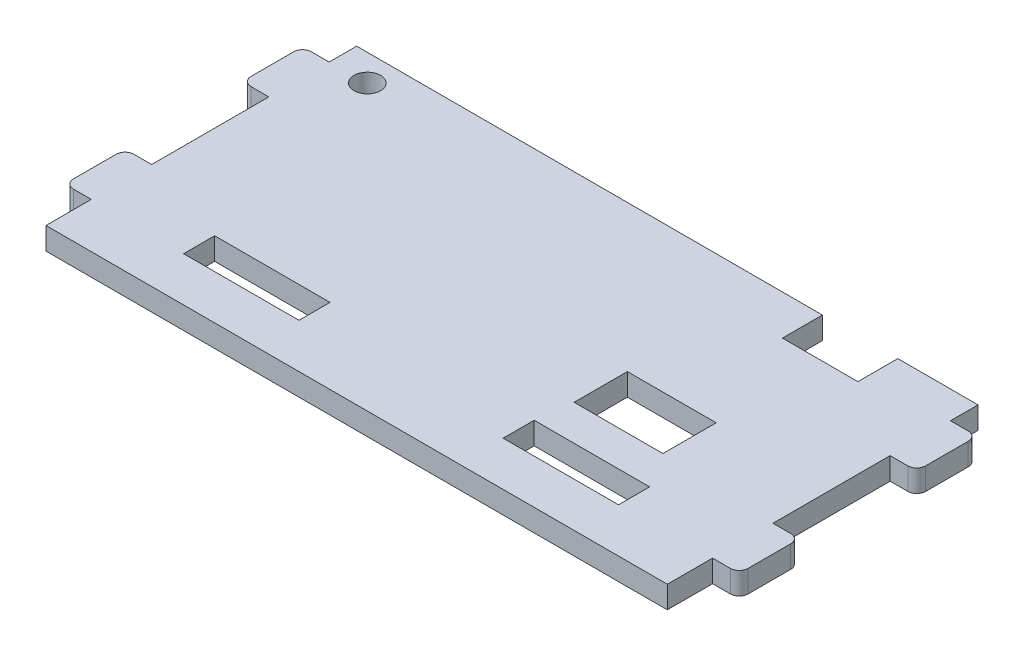
SolidWorks part; units mm, degrees
ref_plane "前视" through (0, 0, 0) normal (0, 0, 1) x (1, 0, 0)
ref_plane "上视" through (0, 0, 0) normal (0, 1, 0) x (1, 0, 0)
ref_plane "右视" through (0, 0, 0) normal (1, 0, 0) x (0, 0, -1)
sketch "草图1" plane through (0, 0, 0) normal (0, 1, 0) x (1, 0, 0)
  line L1 (-38, 17.5) -> (38, 17.5)
  line L2 (-38, 17.5) -> (-38, -17.5)
  line L3 (-38, -17.5) -> (38, -17.5)
  line L4 (38, 17.5) -> (38, -17.5)
  line L5 (-38, 17.5) -> (38, -17.5) construction
  line L6 (-38, -17.5) -> (38, 17.5) construction
  point P0 (0, 0)
  dimension "D1" = 35
  dimension "D2" = 76
extrude "凸台-拉伸1" add sketch "草图1" along normal blind 2.5
sketch "草图2" plane through (0, 2.5, 0) normal (0, 1, 0) x (1, 0, 0)
  line L0 (-38, -17.5) -> (38, -17.5) construction
  line L1 (-24.5, -9) -> (-11.5, -9)
  line L2 (-24.5, -9) -> (-24.5, -12.5)
  line L3 (-24.5, -12.5) -> (-11.5, -12.5)
  line L4 (-11.5, -9) -> (-11.5, -12.5)
  line L5 (-24.5, -9) -> (-11.5, -12.5) construction
  line L6 (-24.5, -12.5) -> (-11.5, -9) construction
  line L7 (-38, 17.5) -> (-38, -17.5) construction
  line L8 (0, 0) -> (0, -2.6782) construction
  line L9 (24.5, -12.5) -> (11.5, -12.5)
  line L10 (11.5, -9) -> (11.5, -12.5)
  line L11 (24.5, -9) -> (11.5, -9)
  line L12 (24.5, -9) -> (24.5, -12.5)
  point P0 (-18, -10.75)
  dimension "D1" = 5
  dimension "D2" = 13.5
  dimension "D3" = 13
  dimension "D4" = 3.5
extrude "切除-拉伸1" cut sketch "草图2" against normal through all
sketch "草图3" plane through (0, 2.5, 0) normal (0, 1, 0) x (1, 0, 0)
  line L0 (-38, -17.5) -> (-35, -17.5)
  line L1 (-38, -17.5) -> (38, -17.5) construction
  line L2 (-35, -17.5) -> (-35, -12.4)
  line L3 (-35, -12.4) -> (-38, -12.4)
  line L4 (-38, 17.5) -> (-38, -17.5) construction
  line L5 (-38, -12.4) -> (-38, -17.5)
  line L6 (-38, 17.5) -> (-35, 17.5)
  line L7 (38, 17.5) -> (-38, 17.5) construction
  line L8 (-35, 17.5) -> (-35, 14.4)
  line L9 (-35, 14.4) -> (-38, 14.4)
  line L10 (-38, 14.4) -> (-38, 17.5)
  line L11 (-38, 7.6) -> (-35, 7.6)
  line L12 (-35, 7.6) -> (-35, -5.6)
  line L13 (-35, -5.6) -> (-38, -5.6)
  line L14 (-38, -5.6) -> (-38, 7.6)
  line L15 (0, 0) -> (0, 5.419) construction
  line L16 (38, -17.5) -> (35, -17.5)
  line L17 (38, -12.4) -> (38, -17.5)
  line L18 (35, -17.5) -> (35, -12.4)
  line L19 (35, -12.4) -> (38, -12.4)
  line L20 (35, -5.6) -> (38, -5.6)
  line L21 (38, -5.6) -> (38, 7.6)
  line L22 (35, 7.6) -> (35, -5.6)
  line L23 (38, 7.6) -> (35, 7.6)
  line L24 (35, 14.4) -> (38, 14.4)
  line L25 (35, 17.5) -> (35, 14.4)
  line L26 (38, 17.5) -> (35, 17.5)
  line L27 (38, 14.4) -> (38, 17.5)
  dimension "D1" = 3
  dimension "D2" = 5.1
  dimension "D3" = 3
  dimension "D4" = 3.1
  dimension "D5" = 3
  dimension "D6" = 6.8
  dimension "D7" = 6.8
extrude "切除-拉伸2" cut sketch "草图3" against normal through all
fillet "圆角1" radius 1 8 edges at (38, 1.25, -14.4) (38, 1.25, -7.6) (38, 1.25, 5.6) (38, 1.25, 12.4) (-38, 1.25, 12.4) (-38, 1.25, 5.6) (-38, 1.25, -7.6) (-38, 1.25, -14.4)
sketch "草图4" plane through (0, 2.5, 0) normal (0, 1, 0) x (1, 0, 0)
  line L0 (35, 17.5) -> (-35, 17.5) construction
  line L1 (35, 17.5) -> (35, 14.4) construction
  line L2 (-35, 14.4) -> (-35, 17.5) construction
  line L3 (18.0812, 14.5) -> (26.9965, 14.5) construction
  line L4 (25.9681, 17.5) -> (25.9681, 13)
  line L5 (25.9681, 13) -> (17.4681, 13)
  line L6 (17.4681, 13) -> (17.4681, 17.5)
  line L7 (17.4681, 17.5) -> (25.9681, 17.5)
  circle A0 centre (-30.8, 14.5) radius 1.5
  point P4 (-35, 15.95)
  dimension "D1" = 3
  dimension "D2" = 4.2
  dimension "D3" = 4.5
  dimension "D4" = 8.5
  dimension "D5" = 9.0319
extrude "切除-拉伸3" cut sketch "草图4" against normal through all
sketch "草图5" plane through (0, 2.5, 0) normal (0, 1, 0) x (1, 0, 0)
  line L0 (35, 7.6) -> (35, -5.6) construction
  line L1 (12, 1) -> (22, 1)
  line L2 (12, 1) -> (12, -5)
  line L3 (12, -5) -> (22, -5)
  line L4 (22, 1) -> (22, -5)
  line L5 (12, 1) -> (22, -5) construction
  line L6 (12, -5) -> (22, 1) construction
  line L7 (24.5, -9) -> (11.5, -9) construction
  point P0 (17, -2)
  dimension "D1" = 10
  dimension "D2" = 6
  dimension "D3" = 18
  dimension "D4" = 7
extrude "切除-拉伸4" cut sketch "草图5" against normal through all
